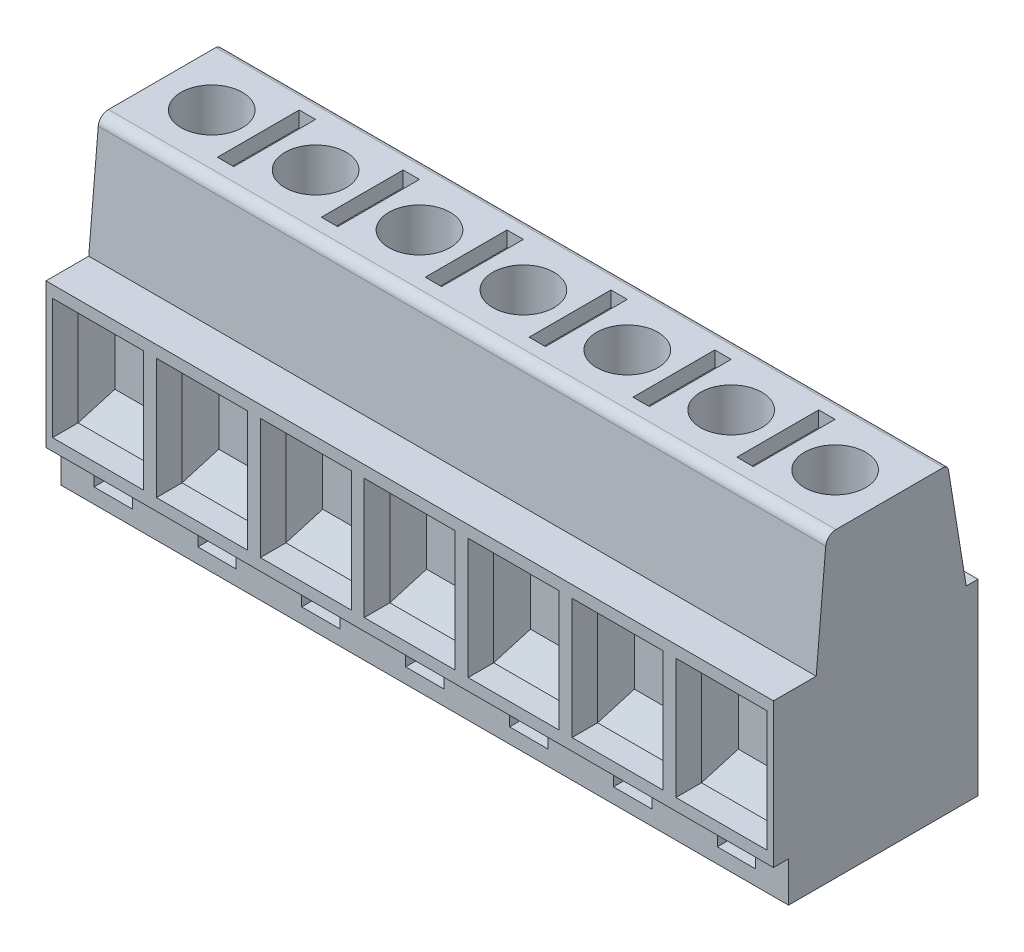
SolidWorks part; units mm, degrees
ref_plane "Front Plane" through (0, 0, 0) normal (0, 0, 1) x (1, 0, 0)
ref_plane "Top Plane" through (0, 0, 0) normal (0, 1, 0) x (1, 0, 0)
ref_plane "Right Plane" through (0, 0, 0) normal (1, 0, 0) x (0, 0, -1)
sketch "Sketch1" plane through (0, 0, 0) normal (1, 0, 0) x (0, 0, -1)
  line L0 (9.6447, 33.3244) -> (29.6447, 33.3244) construction
  line L1 (9.6692, 32.9692) -> (9.6692, 47.0868)
  line L2 (9.6692, 47.0868) -> (13.8475, 47.0868)
  line L3 (13.8475, 47.0868) -> (14.8593, 58.5419)
  line L4 (14.8593, 58.5419) -> (26.709, 58.5419)
  line L5 (26.709, 58.5419) -> (28.5149, 47.3865)
  line L6 (28.5149, 47.3865) -> (29.6692, 47.3865)
  line L7 (29.6692, 47.3865) -> (29.6692, 29.0419)
  line L8 (29.6692, 29.0419) -> (11.1423, 29.0419)
  line L9 (11.1423, 29.0419) -> (11.1423, 32.9692)
  line L10 (11.1423, 32.9692) -> (9.6692, 32.9692)
  line L11 (68.0457, 60.9618) -> (149.3457, 60.9618) construction
  line L12 (139.8559, 49.112) -> (148.7559, 49.112) construction
  line L13 (139.8559, 49.112) -> (139.8559, 37.312) construction
  line L14 (204.1416, 49.112) -> (206.6416, 49.112) construction
  line L15 (208.5587, 45.7504) -> (208.5587, 39.4578) construction
  line L16 (208.5587, 42.6041) -> (206.6416, 42.6041) construction
  line L17 (121.2763, 41.7533) -> (126.7736, 41.7533) construction
  line L18 (217.6919, 61.8593) -> (217.6919, 56.1569) construction
  line L19 (142.8406, 99.3741) -> (145.9297, 99.3741) construction
  line L20 (211.5813, 61.8593) -> (211.5813, 60.3558) construction
  line L21 (118.1896, 87.8673) -> (119.7969, 87.8673) construction
  line L22 (118.1896, 87.8673) -> (118.1896, 95.8627) construction
  line L23 (118.1896, 95.8627) -> (119.7969, 95.8627) construction
  line L24 (119.7969, 87.8673) -> (119.7969, 95.8627) construction
  line L25 (170.4098, 32.3653) -> (173.8098, 32.3653) construction
  line L26 (173.8098, 32.3653) -> (175.1098, 32.3653) construction
  line L27 (175.1098, 32.3653) -> (178.3098, 32.3653) construction
  line L28 (178.3098, 32.3653) -> (179.6098, 32.3653) construction
  line L29 (179.6098, 32.3653) -> (183.0098, 32.3653) construction
  line L30 (183.0098, 32.3653) -> (184.3098, 32.3653) construction
  line L31 (142.4541, 34.5696) -> (146.1866, 34.5696) construction
  line L32 (146.1866, 34.5696) -> (142.4541, 34.5696) construction
  line L33 (142.4541, 34.5696) -> (142.4541, 33.584) construction
  circle A0 centre (134.2519, 91.3377) radius 3.0186 construction
  dimension "D1" = 20
  dimension "D2" = 20
  dimension "D3" = 29.5
  dimension "D4" = 9.6692
  dimension "D5" = 11.1423
  dimension "D6" = 13.8475
  dimension "D7" = 14.8593
  dimension "D8" = 26.709
  dimension "D9" = 28.5149
  dimension "D10" = 29.0419
  dimension "D11" = 32.9692
  dimension "D12" = 33.3244
  dimension "D13" = 47.0868
  dimension "D14" = 47.3865
  dimension "D15" = 81.3
  dimension "D16" = 8.9
  dimension "D17" = 11.8
  dimension "D18" = 2.5
  dimension "D19" = 1.6073
  dimension "D20" = 7.9954
  dimension "D21" = 3.4
  dimension "D22" = 1.3
  dimension "D23" = 3.2
  dimension "D24" = 1.3
  dimension "D25" = 3.4
  dimension "D26" = 1.3
extrude "Boss-Extrude1" add sketch "Sketch1" along normal blind 10.16
sketch "Sketch2" plane through (0, 0, -9.6692) normal (0, 0, 1) x (1, 0, 0)
  line L0 (0, 47.0868) -> (0, 32.9692) construction
  line L1 (0.63, 34.128) -> (9.53, 34.128)
  line L2 (0.63, 34.128) -> (0.63, 45.928)
  line L3 (0.63, 45.928) -> (9.53, 45.928)
  line L4 (9.53, 34.128) -> (9.53, 45.928)
  line L5 (0.63, 34.128) -> (9.53, 45.928) construction
  line L6 (0.63, 45.928) -> (9.53, 34.128) construction
  line L7 (10.16, 47.0868) -> (0, 47.0868) construction
  point P0 (5.08, 40.028)
  point P5 (0, 0)
  point P8 (0, 40.028)
  point P9 (0, 0)
  point P12 (5.08, 47.0868)
  point P13 (9.3089, 45.6013)
  dimension "D1" = 8.9
  dimension "D2" = 11.8
extrude "Cut-Extrude1" cut sketch "Sketch2" against normal blind 2.5
sketch "Sketch3" plane through (0, 0, -12.1692) normal (0, 0, 1) x (1, 0, 0)
  line L4 (9.53, 34.128) -> (9.53, 45.928)
  line L5 (9.53, 45.928) -> (0.63, 45.928)
  line L6 (0.63, 45.928) -> (0.63, 34.128)
  line L7 (0.63, 34.128) -> (9.53, 34.128)
  line L8 (9.53, 34.128) -> (9.53, 45.928)
  line L9 (9.53, 45.928) -> (0.63, 45.928)
  line L10 (0.63, 45.928) -> (0.63, 34.128)
  line L11 (0.63, 34.128) -> (9.53, 34.128)
  dimension "D1" = 0
ref_plane "Plane1" through (0, 0, -14.0692) normal (0, 0, 1) x (1, 0, 0)
sketch "Sketch4" plane through (0, 0, -14.0692) normal (0, 0, 1) x (1, 0, 0)
  line L0 (9.53, 45.928) -> (0.63, 45.928) construction
  line L1 (2.33, 36.878) -> (7.83, 36.878)
  line L2 (2.33, 36.878) -> (2.33, 43.178)
  line L3 (2.33, 43.178) -> (7.83, 43.178)
  line L4 (7.83, 36.878) -> (7.83, 43.178)
  line L5 (2.33, 36.878) -> (7.83, 43.178) construction
  line L6 (2.33, 43.178) -> (7.83, 36.878) construction
  line L7 (0.63, 45.928) -> (0.63, 34.128) construction
  point P0 (5.08, 40.028)
  point P5 (0, 0)
  point P8 (5.08, 45.928)
  point P9 (0, 0)
  point P12 (0.63, 40.028)
  dimension "D1" = 6.3
  dimension "D2" = 5.5
loft "Cut-Loft1" cut profiles "Sketch3", "Sketch4" connector at (0.63, 45.928, -12.1692) connector at (2.33, 43.178, -14.0692)
sketch "Sketch5" plane through (0, 58.5419, 0) normal (0, 1, 0) x (1, 0, 0)
  line L0 (10.16, 26.709) -> (10.16, 14.8593) construction
  line L1 (10.16, 29.6692) -> (0, 29.6692) construction
  circle A0 centre (5.08, 20.7842) radius 3
  point P2 (0, 0)
  point P5 (10.16, 20.7842)
  point P6 (0, 0)
  point P9 (5.08, 29.6692)
  dimension "D1" = 6
extrude "Cut-Extrude2" cut sketch "Sketch5" against normal blind 5.7
sketch "Sketch7" plane through (0, 29.0419, 0) normal (0, -1, 0) x (1, 0, 0)
  line L0 (10.16, -11.1423) -> (0, -11.1423) construction
  line L1 (4.43, -27.5692) -> (5.73, -27.5692)
  line L2 (4.43, -27.5692) -> (4.43, -26.7692)
  line L3 (4.43, -26.7692) -> (5.73, -26.7692)
  line L4 (5.73, -27.5692) -> (5.73, -26.7692)
  line L5 (4.43, -27.5692) -> (5.73, -26.7692) construction
  line L6 (4.43, -26.7692) -> (5.73, -27.5692) construction
  line L7 (4.43, -17.4092) -> (5.73, -17.4092)
  line L8 (4.43, -17.4092) -> (4.43, -16.6092)
  line L9 (4.43, -16.6092) -> (5.73, -16.6092)
  line L10 (5.73, -17.4092) -> (5.73, -16.6092)
  line L11 (4.43, -17.4092) -> (5.73, -16.6092) construction
  line L12 (4.43, -16.6092) -> (5.73, -17.4092) construction
  line L13 (10.16, -29.6692) -> (0, -29.6692) construction
  point P0 (5.08, -27.1692)
  point P5 (5.08, -17.0092)
  point P10 (0, 0)
  point P13 (5.08, -11.1423)
  dimension "D1" = 1.3
  dimension "D2" = 0.8
  dimension "D3" = 2.5
  dimension "D4" = 10.16
extrude "Boss-Extrude2" add sketch "Sketch7" along normal blind 4.5
sketch "Sketch8" plane through (0, 0, -16.6092) normal (0, 0, 1) x (1, 0, 0)
  line L0 (4.43, 24.5419) -> (4.43, 29.0419) construction
  line L1 (5.73, 24.5419) -> (5.73, 29.0419) construction
  line L2 (5.73, 24.5419) -> (4.43, 24.5419) construction
  arc A0 (4.43, 25.1919) -> (5.73, 25.1919) centre (5.08, 25.1919) ccw
  point P3 (5.08, 24.5419)
extrude "Cut-Extrude5" cut sketch "Sketch8" against normal through all flip side to cut
ref_plane "Plane2" through (0, 38.5279, -38.5279) normal (0, 0.7071, -0.7071) x (-1, 0, 0)
sketch "Sketch10" plane through (0, 38.5279, -38.5279) normal (0, 0.7071, -0.7071) x (-1, 0, 0)
  line L0 (-10.16, 12.528) -> (0, 12.528) construction
  circle A0 centre (-5.08, 12.528) radius 1.5
  dimension "D1" = 3
extrude "Cut-Extrude6" cut sketch "Sketch10" against normal blind 4.5 contours A0
sketch "Sketch13" plane through (0, 0, -11.1423) normal (0, 0, 1) x (1, 0, 0)
  line L0 (10.16, 32.9692) -> (10.16, 29.0419) construction
  line L1 (3.205, 30.5055) -> (6.955, 30.5055)
  line L2 (3.205, 30.5055) -> (3.205, 31.5055)
  line L3 (3.205, 31.5055) -> (6.955, 31.5055)
  line L4 (6.955, 30.5055) -> (6.955, 31.5055)
  line L5 (3.205, 30.5055) -> (6.955, 31.5055) construction
  line L6 (3.205, 31.5055) -> (6.955, 30.5055) construction
  line L7 (10.16, 32.9692) -> (0, 32.9692) construction
  point P0 (5.08, 31.0055)
  point P5 (0, 0)
  point P8 (10.16, 31.0055)
  point P9 (0, 0)
  point P12 (5.08, 32.9692)
  dimension "D1" = 3.75
  dimension "D2" = 1
extrude "Cut-Extrude8" cut sketch "Sketch13" against normal blind 3
fillet "Fillet3" radius 0.5 1 edges at (5.08, 58.5419, -26.709) type face fillet first side face at (5.08, 58.5419, -17.7842) second side face at (5.08, 51.2437, -27.8905)
fillet "Fillet4" radius 1 1 edges at (5.08, 58.5419, -14.8593) type face fillet first side face at (5.08, 58.5419, -17.7842) second side face at (5.08, 52.8143, -14.3534)
sketch "Sketch12" plane through (0, 29.0419, 0) normal (0, -1, 0) x (1, 0, 0)
  line L1 (-0.65, -15.8423) -> (0.65, -15.8423)
  line L2 (-0.65, -15.8423) -> (-0.65, -14.5423)
  line L3 (-0.65, -14.5423) -> (0.65, -14.5423)
  line L4 (0.65, -15.8423) -> (0.65, -14.5423)
  line L5 (-0.65, -15.8423) -> (0.65, -14.5423) construction
  line L6 (-0.65, -14.5423) -> (0.65, -15.8423) construction
  line L8 (-0.65, -20.3423) -> (0.65, -20.3423)
  line L9 (-0.65, -20.3423) -> (-0.65, -19.0423)
  line L10 (-0.65, -19.0423) -> (0.65, -19.0423)
  line L11 (0.65, -20.3423) -> (0.65, -19.0423)
  line L12 (-0.65, -20.3423) -> (0.65, -19.0423) construction
  line L13 (-0.65, -19.0423) -> (0.65, -20.3423) construction
  line L14 (-0.65, -25.0423) -> (0.65, -25.0423)
  line L15 (-0.65, -25.0423) -> (-0.65, -23.7423)
  line L16 (-0.65, -23.7423) -> (0.65, -23.7423)
  line L17 (0.65, -25.0423) -> (0.65, -23.7423)
  line L18 (-0.65, -25.0423) -> (0.65, -23.7423) construction
  line L19 (-0.65, -23.7423) -> (0.65, -25.0423) construction
  line L20 (10.16, -11.1423) -> (0, -11.1423) construction
  line L21 (0, -11.1423) -> (0, -29.6692) construction
  point P0 (0, -15.1923)
  point P5 (0, 0)
  point P6 (0, -15.1923)
  point P7 (0, -19.6923)
  point P12 (0, -24.3923)
  point P21 (0, 0)
  point P22 (0, 0)
  point P23 (0, -15.1923)
  point P24 (0, -19.6923)
  point P25 (0, -24.3923)
  dimension "D1" = 3.4
  dimension "D2" = 1.3
  dimension "D3" = 3.2
  dimension "D4" = 3.4
  dimension "D5" = 1.3
extrude "Boss-Extrude3" add sketch "Sketch12" along normal blind 0.5 separate body
sketch "Sketch14" plane through (10.16, 0, 0) normal (1, 0, 0) x (0, 0, -1)
  line L10 (26.2835, 58.5419) -> (15.7749, 58.5419)
  line L11 (14.7788, 57.6298) -> (13.8475, 47.0868)
  line L12 (13.8475, 47.0868) -> (9.6692, 47.0868)
  line L13 (9.6692, 47.0868) -> (9.6692, 32.9692)
  line L14 (9.6692, 32.9692) -> (11.1423, 32.9692)
  line L15 (11.1423, 32.9692) -> (11.1423, 29.0419)
  line L16 (11.1423, 29.0419) -> (29.6692, 29.0419)
  line L17 (29.6692, 29.0419) -> (29.6692, 47.3865)
  line L18 (29.6692, 47.3865) -> (28.5149, 47.3865)
  line L19 (28.5149, 47.3865) -> (26.777, 58.1218)
  line L21 (14.7788, 57.6298) -> (13.8475, 47.0868)
  line L22 (13.8475, 47.0868) -> (9.6692, 47.0868)
  line L23 (9.6692, 47.0868) -> (9.6692, 32.9692)
  line L24 (9.6692, 32.9692) -> (11.1423, 32.9692)
  line L25 (11.1423, 32.9692) -> (11.1423, 29.0419)
  line L26 (11.1423, 29.0419) -> (29.6692, 29.0419)
  line L27 (29.6692, 29.0419) -> (29.6692, 47.3865)
  line L28 (29.6692, 47.3865) -> (28.5149, 47.3865)
  line L29 (28.5149, 47.3865) -> (26.777, 58.1218)
  line L31 (26.2835, 58.5419) -> (15.7749, 58.5419)
  arc A3 (26.777, 58.1218) -> (26.2835, 58.5419) centre (26.2835, 58.0419) ccw
  arc A6 (26.777, 58.1218) -> (26.2835, 58.5419) centre (26.2835, 58.0419) ccw
  arc A8 (15.7749, 58.5419) -> (14.7788, 57.6298) centre (15.7749, 57.5419) ccw
  arc A9 (15.7749, 58.5419) -> (14.7788, 57.6298) centre (15.7749, 57.5419) ccw
  dimension "D1" = 0
extrude "Boss-Extrude4" add sketch "Sketch14" along normal blind 0.01
ref_plane "Plane3" through (0, 0, 0) normal (-1, 0, 0) x (0, 0, 1)
pattern_linear "LPattern8" count 7 spacing 10.16 along (-1, 0, 0) of "Boss-Extrude1", "Cut-Extrude1", "Cut-Loft1", "Cut-Extrude2", "Boss-Extrude2", "Cut-Extrude5", "Cut-Extrude6", "Cut-Extrude8", "Fillet3", "Fillet4"
sketch "Sketch11" plane through (0, 58.5419, 0) normal (0, 1, 0) x (1, 0, 0)
  line L1 (-0.8, 17.0641) -> (0.8, 17.0641)
  line L2 (-0.8, 17.0641) -> (-0.8, 25.0641)
  line L3 (-0.8, 25.0641) -> (0.8, 25.0641)
  line L4 (0.8, 17.0641) -> (0.8, 25.0641)
  line L5 (-0.8, 17.0641) -> (0.8, 25.0641) construction
  line L6 (-0.8, 25.0641) -> (0.8, 17.0641) construction
  line L8 (0, 55) -> (0, -55) construction
  point P0 (0, 21.0641)
  point P5 (1.8522, 20.6032)
  point P6 (1.6707, 20.773)
  point P7 (0, 0)
  point P8 (0, 0)
  point P12 (0, 0)
  point P13 (0.3317, 21.0641)
  point P16 (0, 0)
  dimension "D1" = 1.6
  dimension "D2" = 8
extrude "Cut-Extrude7" cut sketch "Sketch11" against normal blind 1.5
pattern_linear "LPattern9" count 6 spacing 10.16 along (-1, 0, 0) of "Boss-Extrude3", "Cut-Extrude7"
sketch "Sketch16" plane through (-60.96, 0, 0) normal (-1, 0, 0) x (0, 0, 1)
  line L10 (-13.8475, 47.0868) -> (-14.7788, 57.6298)
  line L11 (-15.7749, 58.5419) -> (-26.2835, 58.5419)
  line L12 (-26.777, 58.1218) -> (-28.5149, 47.3865)
  line L13 (-28.5149, 47.3865) -> (-29.6692, 47.3865)
  line L14 (-29.6692, 47.3865) -> (-29.6692, 29.0419)
  line L15 (-29.6692, 29.0419) -> (-11.1423, 29.0419)
  line L16 (-11.1423, 29.0419) -> (-11.1423, 32.9692)
  line L17 (-11.1423, 32.9692) -> (-9.6692, 32.9692)
  line L18 (-9.6692, 32.9692) -> (-9.6692, 47.0868)
  line L19 (-9.6692, 47.0868) -> (-13.8475, 47.0868)
  line L82 (-13.8475, 47.0868) -> (-14.7788, 57.6298)
  line L83 (-15.7749, 58.5419) -> (-26.2835, 58.5419)
  line L84 (-26.777, 58.1218) -> (-28.5149, 47.3865)
  line L85 (-28.5149, 47.3865) -> (-29.6692, 47.3865)
  line L86 (-29.6692, 47.3865) -> (-29.6692, 29.0419)
  line L87 (-29.6692, 29.0419) -> (-11.1423, 29.0419)
  line L88 (-11.1423, 29.0419) -> (-11.1423, 32.9692)
  line L89 (-11.1423, 32.9692) -> (-9.6692, 32.9692)
  line L90 (-9.6692, 32.9692) -> (-9.6692, 47.0868)
  line L91 (-9.6692, 47.0868) -> (-13.8475, 47.0868)
  arc A2 (-14.7788, 57.6298) -> (-15.7749, 58.5419) centre (-15.7749, 57.5419) ccw
  arc A8 (-26.2835, 58.5419) -> (-26.777, 58.1218) centre (-26.2835, 58.0419) ccw
  arc A18 (-14.7788, 57.6298) -> (-15.7749, 58.5419) centre (-15.7749, 57.5419) ccw
  arc A19 (-26.2835, 58.5419) -> (-26.777, 58.1218) centre (-26.2835, 58.0419) ccw
  dimension "D1" = 0
extrude "Boss-Extrude6" add sketch "Sketch16" along normal blind 0.01
